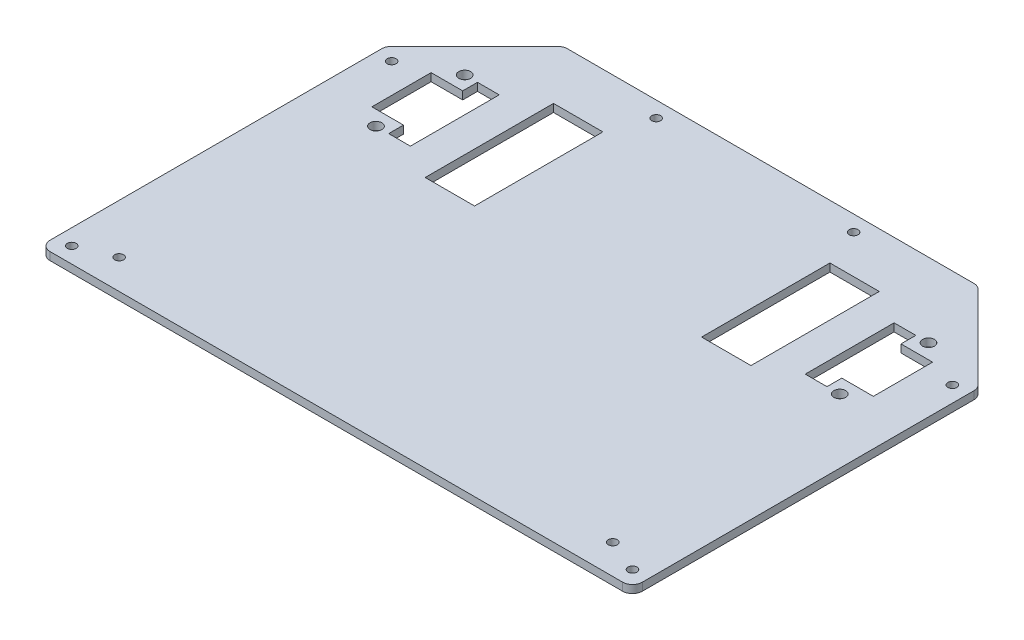
SolidWorks part; units mm, degrees
material "Acier non allié"
ref_plane "Front" through (0, 0, 0) normal (0, 0, 1) x (1, 0, 0)
ref_plane "Top" through (0, 0, 0) normal (0, 1, 0) x (1, 0, 0)
ref_plane "Right" through (0, 0, 0) normal (1, 0, 0) x (0, 0, -1)
sketch "Main scetch" plane through (0, 0, 0) normal (0, 1, 0) x (1, 0, 0)
  line L0 (-150, 0) -> (150, 0)
  line L1 (0, 0) -> (150, 0) construction
  line L2 (0, 0) -> (0, 220) construction
  line L3 (0, 220) -> (150, 220) construction
  line L4 (150, 0) -> (150, 220) construction
  line L5 (150, 0) -> (150, 175)
  line L6 (150, 175) -> (105, 220)
  line L10 (105, 220) -> (-105, 220)
  line L11 (-150, 0) -> (-150, 175)
  line L12 (-150, 175) -> (-105, 220)
  dimension "D1" = 150
  dimension "D2" = 220
  dimension "D3" = 45
  dimension "D4" = 45
extrude "Main extrusion" add sketch "Main scetch" along normal blind 4
fillet "Corner leave" radius 5 6 edges at (-150, 2, 0) (150, 2, -175) (105, 2, -220) (150, 2, 0) (-105, 2, -220) (-150, 2, -175)
sketch "Esquisse2" plane through (0, 4, 0) normal (0, 1, 0) x (1, 0, 0)
  line L0 (-145, 0) -> (145, 0) construction
  line L1 (150, 5) -> (150, 172.9289) construction
  line L2 (148.5355, 176.4645) -> (106.4645, 218.5355) construction
  line L3 (102.9289, 220) -> (-102.9289, 220) construction
  line L4 (-106.4645, 218.5355) -> (-148.5355, 176.4645) construction
  line L5 (-150, 172.9289) -> (-150, 5) construction
  line L6 (-145, 0) -> (145, 0) construction
  line L7 (150, 5) -> (150, 172.9289) construction
  line L8 (148.5355, 176.4645) -> (106.4645, 218.5355) construction
  line L9 (102.9289, 220) -> (-102.9289, 220) construction
  line L10 (-106.4645, 218.5355) -> (-148.5355, 176.4645) construction
  line L11 (-150, 172.9289) -> (-150, 5) construction
  line L12 (0, 0) -> (0, 238.9669) construction
  line L13 (0, 160) -> (165.6987, 160) construction
  line L14 (70, 230.4421) -> (70, 102.0601) construction
  line L15 (57.5, 192.5) -> (82.5, 192.5)
  line L16 (57.5, 192.5) -> (57.5, 127.5)
  line L17 (57.5, 127.5) -> (82.5, 127.5)
  line L18 (82.5, 192.5) -> (82.5, 127.5)
  line L19 (100, 137.5) -> (100, 182.5)
  line L20 (100, 182.5) -> (111, 182.5)
  line L22 (127, 175) -> (127, 145)
  line L23 (100, 137.5) -> (111, 137.5)
  line L35 (111, 182.5) -> (111, 175)
  line L36 (111, 175) -> (127, 175)
  line L37 (111, 137.5) -> (111, 145)
  line L38 (111, 145) -> (127, 145)
  line L39 (-111, 137.5) -> (-111, 145)
  line L40 (-100, 137.5) -> (-111, 137.5)
  line L41 (-100, 137.5) -> (-100, 182.5)
  line L42 (-100, 182.5) -> (-111, 182.5)
  line L43 (-111, 182.5) -> (-111, 175)
  line L44 (-111, 175) -> (-127, 175)
  line L45 (-127, 175) -> (-127, 145)
  line L46 (-111, 145) -> (-127, 145)
  line L47 (-57.5, 127.5) -> (-82.5, 127.5)
  line L48 (-82.5, 192.5) -> (-82.5, 127.5)
  line L49 (-57.5, 192.5) -> (-82.5, 192.5)
  line L50 (-57.5, 192.5) -> (-57.5, 127.5)
  circle A0 centre (117.47, 182.47) radius 3
  circle A1 centre (117.47, 137.53) radius 3
  circle A2 centre (-117.47, 137.53) radius 3
  circle A3 centre (-117.47, 182.47) radius 3
  point P28 (127, 160)
  point P29 (100, 160)
  dimension "D12" = 6
  dimension "D1" = 60
  dimension "D2" = 65
  dimension "D3" = 70
  dimension "D4" = 25
  dimension "D5" = 27
  dimension "D6" = 45
  dimension "D7" = 100
  dimension "D8" = 11
  dimension "D9" = 30
  dimension "D10" = 17.47
  dimension "D11" = 22.47
extrude "Enlèv. mat.-Extru.1" cut sketch "Esquisse2" against normal through all
sketch "Esquisse8" plane through (0, 4, 0) normal (0, 1, 0) x (1, 0, 0)
  line L0 (-150, 172.9289) -> (-150, 5) construction
  line L1 (-145, 0) -> (145, 0) construction
  line L3 (150, 5) -> (150, 172.9289) construction
  circle A0 centre (-125, 15) radius 1.5
  circle A1 centre (125, 15) radius 1.5
  dimension "D1" = 3
  dimension "D4" = 3
  dimension "D6" = 25
  dimension "D2" = 25
  dimension "D3" = 15
  dimension "D5" = 15
hole_wizard "Dégagement M41" positions "Esquisse16" profile "Esquisse17" hole size "M4" standard "ISO" end condition through all
sketch "Esquisse16" plane through (0, 4, 0) normal (0, 1, 0) x (1, 0, 0)
  point P0 (-125, 15)
  point P3 (125, 15)
sketch "Esquisse17" plane through (-125, 4, -15) normal (1, 0, 0) x (0, 0, 1)
  line L0 (0, 0) -> (0, 4)
  line L1 (0, 4) -> (2.25, 4)
  line L2 (2.25, 4) -> (2.25, 0)
  line L5 (2.25, 0) -> (0, 0)
  line L11 (0, -6.35) -> (0, 107.95) construction
  dimension "Diamètre du perçage jusqu'au prochain" = 4.5
  dimension "Profondeur du perçage jusqu'au prochain" = 4
sketch "Esquisse18" plane through (0, 4, 0) normal (0, 1, 0) x (1, 0, 0)
  line L0 (-150, 172.9289) -> (-150, 5) construction
  line L1 (-145, 0) -> (145, 0) construction
  line L2 (102.9289, 220) -> (-102.9289, 220) construction
  line L3 (150, 5) -> (150, 172.9289) construction
  circle A0 centre (-142, 8) radius 1
  circle A1 centre (-142, 170) radius 1
  circle A2 centre (-50, 212) radius 1
  circle A3 centre (50, 212) radius 1
  circle A4 centre (142, 170) radius 1
  circle A5 centre (142, 8) radius 1
  dimension "D1" = 2
  dimension "D2" = 2
  dimension "D3" = 2
  dimension "D4" = 2
  dimension "D5" = 2
  dimension "D6" = 2
  dimension "D7" = 8
  dimension "D8" = 8
  dimension "D9" = 170
  dimension "D10" = 8
  dimension "D11" = 8
  dimension "D12" = 50
  dimension "D13" = 8
  dimension "D14" = 50
  dimension "D15" = 8
  dimension "D16" = 170
  dimension "D17" = 8
  dimension "D18" = 8
hole_wizard "Dégagement M42" positions "Esquisse3D1" profile "Esquisse19" hole size "M4" standard "ISO" end condition through all
sketch3d "Esquisse3D1"
  point P0 (-142, 4, -8)
  point P3 (-142, 4, -170)
  point P6 (-50, 4, -212)
  point P9 (50, 4, -212)
  point P12 (142, 4, -170)
  point P14 (142, 4, -8)
  point P17 (142, 4, -170)
sketch "Esquisse19" plane through (-142, 4, -8) normal (1, 0, 0) x (0, 0, 1)
  line L0 (0, 0) -> (0, 4)
  line L1 (0, 4) -> (2.25, 4)
  line L2 (2.25, 4) -> (2.25, 0)
  line L5 (2.25, 0) -> (0, 0)
  line L11 (0, -6.35) -> (0, 107.95) construction
  dimension "Diamètre du perçage jusqu'au prochain" = 4.5
  dimension "Profondeur du perçage jusqu'au prochain" = 4
equation "\"WIDTH\"= 300mm'Total width of the robot"
equation "\"LENGTH\"= 220mm'Total length of the robot"
equation "\"D1@Main scetch\" = \"WIDTH\" / 2"
equation "\"D2@Main scetch\" = \"LENGTH\""
equation "\"CUT_DEPTH\"= 45mm'Depth of the cut on the edges of the plate"
equation "\"D3@Main scetch\" = \"CUT_DEPTH\""
equation "\"D4@Main scetch\" = \"CUT_DEPTH\""
equation "\"Plate_th\"= 3mm'Thickness of the plate"
equation "\"D1\"= \"Plate_th\""
